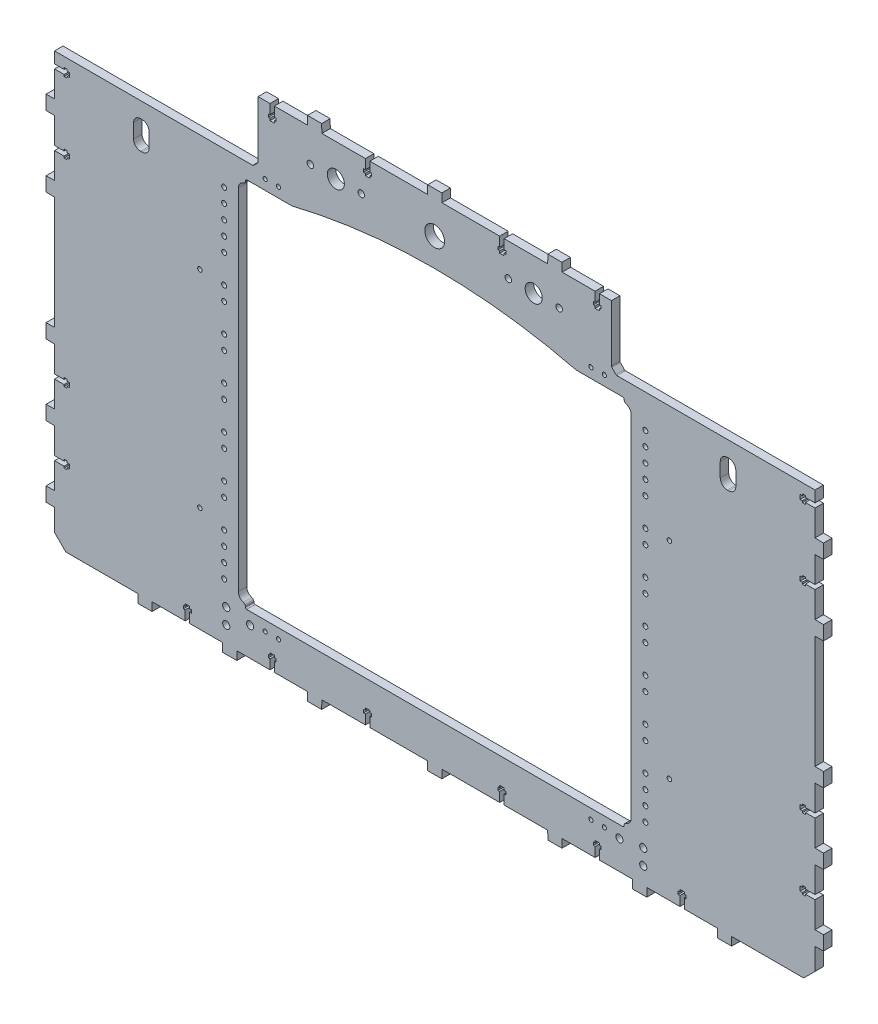
SolidWorks part; units mm, degrees
material "Клен"
ref_plane "Front" through (0, 0, 0) normal (0, 0, 1) x (1, 0, 0)
ref_plane "Top" through (0, 0, 0) normal (0, 1, 0) x (1, 0, 0)
ref_plane "Right" through (0, 0, 0) normal (1, 0, 0) x (0, 0, -1)
sketch "Эскиз1" plane through (0, 0, 0) normal (0, 0, 1) x (1, 0, 0)
  line L0 (1859.5805, 14.5374) -> (1859.5805, 267.5072) construction
  line L1 (1846.6822, 122.5572) -> (1912.7745, 122.5572) construction
  line L2 (1846.6822, 268.5572) -> (1912.7745, 268.5572) construction
  line L3 (1859.5805, 267.5072) -> (1859.5805, 273.1347) construction
  line L6 (1560.5805, 76.7865) -> (1826.5797, 76.7865)
  line L7 (1827.5797, 78.0783) -> (1827.5797, 77.7865)
  line L8 (1832.5805, 332.0072) -> (1832.5797, 84.7865)
  line L9 (1827.5805, 339.0072) -> (1827.5805, 338.7154)
  line L10 (1826.5805, 340.0072) -> (1793.6805, 340.0072)
  line L11 (1560.5805, 340.0072) -> (1592.5638, 340.0072)
  line L13 (1559.5805, 339.0072) -> (1559.5805, 338.7154)
  line L15 (1554.5805, 84.7865) -> (1554.5805, 332.0072)
  line L17 (1559.5805, 78.0783) -> (1559.5805, 77.7865)
  line L18 (1524.5805, 401.0072) -> (1524.5805, 24.1014) construction
  line L19 (1862.5805, 416.6106) -> (1862.5805, 5.7676) construction
  line L20 (1424.5805, 401.0072) -> (1424.5805, 24.1014) construction
  line L21 (1962.5805, 416.6106) -> (1962.5805, 5.7676) construction
  line L22 (1433.5805, 343.0572) -> (1435.0805, 343.0572)
  line L23 (1433.5805, 289.9572) -> (1433.5805, 288.7572)
  line L24 (1433.5805, 149.9572) -> (1433.5805, 148.7572)
  line L25 (1424.5805, 121.4072) -> (1424.5805, 103.0572)
  line L26 (1431.3805, 293.0572) -> (1431.3805, 294.2572)
  line L27 (1431.3805, 154.2572) -> (1433.5805, 154.2572)
  line L28 (1418.5805, 71.5072) -> (1424.5805, 71.4072)
  line L29 (1418.5805, 321.5072) -> (1418.5805, 311.5072)
  line L30 (1418.5805, 311.5072) -> (1424.5805, 311.4072)
  line L31 (1424.5805, 149.9572) -> (1424.5805, 131.6072)
  line L32 (1418.5805, 81.5072) -> (1418.5805, 71.5072)
  line L33 (1433.5805, 338.7572) -> (1431.3805, 338.7572)
  line L34 (1424.5805, 293.0572) -> (1431.3805, 293.0572)
  line L35 (1424.5805, 153.0572) -> (1431.3805, 153.0572)
  line L36 (1433.5805, 103.0572) -> (1435.0805, 103.0572)
  line L37 (1424.5805, 99.9572) -> (1424.5805, 81.6072)
  line L38 (1424.5805, 321.6072) -> (1418.5805, 321.5072)
  line L39 (1433.5805, 293.0572) -> (1435.0805, 293.0572)
  line L40 (1433.5805, 148.7572) -> (1431.3805, 148.7572)
  line L41 (1435.0805, 343.0572) -> (1435.0805, 339.9572)
  line L42 (1431.3805, 289.9572) -> (1424.5805, 289.9572)
  line L43 (1424.5805, 181.6072) -> (1418.5805, 181.5072)
  line L44 (1431.3805, 103.0572) -> (1431.3805, 104.2572)
  line L45 (1435.0805, 103.0572) -> (1435.0805, 99.9572)
  line L46 (1431.3805, 343.0572) -> (1431.3805, 344.2572)
  line L47 (1424.5805, 261.4072) -> (1424.5805, 181.6072)
  line L48 (1433.5805, 153.0572) -> (1435.0805, 153.0572)
  line L49 (1424.5805, 103.0572) -> (1431.3805, 103.0572)
  line L50 (1433.5805, 104.2572) -> (1433.5805, 103.0572)
  line L51 (1424.5805, 311.4072) -> (1424.5805, 293.0572)
  line L52 (1433.5805, 294.2572) -> (1433.5805, 293.0572)
  line L53 (1424.5805, 131.6072) -> (1418.5805, 131.5072)
  line L54 (1431.3805, 338.7572) -> (1431.3805, 339.9572)
  line L55 (1418.5805, 271.5072) -> (1418.5805, 261.5072)
  line L56 (1433.5805, 154.2572) -> (1433.5805, 153.0572)
  line L57 (1433.5805, 98.7572) -> (1431.3805, 98.7572)
  line L58 (1424.5805, 81.6072) -> (1418.5805, 81.5072)
  line L59 (1424.5805, 343.0572) -> (1431.3805, 343.0572)
  line L60 (1431.3805, 339.9572) -> (1424.5805, 339.9572)
  line L61 (1435.0805, 289.9572) -> (1433.5805, 289.9572)
  line L62 (1431.3805, 148.7572) -> (1431.3805, 149.9572)
  line L63 (1435.0805, 339.9572) -> (1433.5805, 339.9572)
  line L64 (1431.3805, 294.2572) -> (1433.5805, 294.2572)
  line L65 (1424.5805, 289.9572) -> (1424.5805, 271.6072)
  line L66 (1433.5805, 99.9572) -> (1433.5805, 98.7572)
  line L67 (1431.3805, 98.7572) -> (1431.3805, 99.9572)
  line L68 (1433.5805, 344.2572) -> (1433.5805, 343.0572)
  line L69 (1424.5805, 271.6072) -> (1418.5805, 271.5072)
  line L70 (1435.0805, 153.0572) -> (1435.0805, 149.9572)
  line L71 (1424.5805, 71.4072) -> (1424.5805, 56.0072)
  line L72 (1431.3805, 344.2572) -> (1433.5805, 344.2572)
  line L73 (1435.0805, 293.0572) -> (1435.0805, 289.9572)
  line L74 (1433.5805, 288.7572) -> (1431.3805, 288.7572)
  line L75 (1418.5805, 131.5072) -> (1418.5805, 121.5072)
  line L76 (1435.0805, 99.9572) -> (1433.5805, 99.9572)
  line L77 (1424.5805, 351.0072) -> (1424.5805, 343.0572)
  line L78 (1418.5805, 171.5072) -> (1424.5805, 171.4072)
  line L79 (1418.5805, 121.5072) -> (1424.5805, 121.4072)
  line L80 (1431.3805, 104.2572) -> (1433.5805, 104.2572)
  line L81 (1431.3805, 288.7572) -> (1431.3805, 289.9572)
  line L82 (1424.5805, 171.4072) -> (1424.5805, 153.0572)
  line L83 (1431.3805, 149.9572) -> (1424.5805, 149.9572)
  line L84 (1433.5805, 339.9572) -> (1433.5805, 338.7572)
  line L85 (1418.5805, 261.5072) -> (1424.5805, 261.4072)
  line L86 (1418.5805, 181.5072) -> (1418.5805, 171.5072)
  line L87 (1431.3805, 99.9572) -> (1424.5805, 99.9572)
  line L88 (1424.5805, 339.9572) -> (1424.5805, 321.6072)
  line L89 (1431.3805, 153.0572) -> (1431.3805, 154.2572)
  line L90 (1435.0805, 149.9572) -> (1433.5805, 149.9572)
  line L91 (1424.5805, 56.0072) -> (1432.5805, 48.0072)
  line L92 (1424.5805, 351.0072) -> (1524.5805, 351.0072)
  line L93 (1432.5805, 48.0072) -> (1483.4805, 48.0072)
  line L94 (1953.5805, 99.9572) -> (1952.0805, 99.9572)
  line L95 (1955.7805, 154.2572) -> (1955.7805, 153.0572)
  line L96 (1953.5805, 289.9572) -> (1952.0805, 289.9572)
  line L97 (1953.5805, 343.0572) -> (1953.5805, 344.2572)
  line L98 (1962.5805, 99.9572) -> (1955.7805, 99.9572)
  line L99 (1955.7805, 153.0572) -> (1962.5805, 153.0572)
  line L100 (1953.5805, 294.2572) -> (1955.7805, 294.2572)
  line L101 (1955.7805, 338.7572) -> (1953.5805, 338.7572)
  line L102 (1953.5805, 103.0572) -> (1953.5805, 104.2572)
  line L103 (1952.0805, 153.0572) -> (1953.5805, 153.0572)
  line L104 (1955.7805, 288.7572) -> (1953.5805, 288.7572)
  line L105 (1962.5805, 321.6072) -> (1962.5805, 339.9572)
  line L106 (1955.7805, 344.2572) -> (1955.7805, 343.0572)
  line L107 (1968.5805, 131.5072) -> (1962.5805, 131.6072)
  line L108 (1962.5805, 149.9572) -> (1955.7805, 149.9572)
  line L109 (1968.5805, 261.5072) -> (1968.5805, 271.5072)
  line L110 (1962.5805, 289.9572) -> (1955.7805, 289.9572)
  line L111 (1955.7805, 343.0572) -> (1962.5805, 343.0572)
  line L112 (1952.0805, 99.9572) -> (1952.0805, 103.0572)
  line L113 (1955.7805, 149.9572) -> (1955.7805, 148.7572)
  line L114 (1952.0805, 293.0572) -> (1953.5805, 293.0572)
  line L115 (1953.5805, 339.9572) -> (1952.0805, 339.9572)
  line L116 (1962.5805, 56.0072) -> (1962.5805, 71.4072)
  line L117 (1955.7805, 103.0572) -> (1962.5805, 103.0572)
  line L118 (1968.5805, 181.5072) -> (1962.5805, 181.6072)
  line L119 (1955.7805, 293.0572) -> (1962.5805, 293.0572)
  line L120 (1953.5805, 344.2572) -> (1955.7805, 344.2572)
  line L121 (1962.5805, 71.4072) -> (1968.5805, 71.5072)
  line L122 (1962.5805, 131.6072) -> (1962.5805, 149.9572)
  line L123 (1968.5805, 171.5072) -> (1968.5805, 181.5072)
  line L124 (1968.5805, 271.5072) -> (1962.5805, 271.6072)
  line L125 (1953.5805, 104.2572) -> (1955.7805, 104.2572)
  line L126 (1953.5805, 153.0572) -> (1953.5805, 154.2572)
  line L127 (1953.5805, 293.0572) -> (1953.5805, 294.2572)
  line L128 (1953.5805, 98.7572) -> (1953.5805, 99.9572)
  line L129 (1962.5805, 121.4072) -> (1968.5805, 121.5072)
  line L130 (1962.5805, 261.4072) -> (1968.5805, 261.5072)
  line L131 (1952.0805, 289.9572) -> (1952.0805, 293.0572)
  line L132 (1952.0805, 343.0572) -> (1953.5805, 343.0572)
  line L133 (1968.5805, 81.5072) -> (1962.5805, 81.6072)
  line L134 (1955.7805, 148.7572) -> (1953.5805, 148.7572)
  line L135 (1962.5805, 293.0572) -> (1962.5805, 311.4072)
  line L136 (1952.0805, 339.9572) -> (1952.0805, 343.0572)
  line L137 (1955.7805, 98.7572) -> (1953.5805, 98.7572)
  line L138 (1962.5805, 103.0572) -> (1962.5805, 121.4072)
  line L139 (1962.5805, 181.6072) -> (1962.5805, 261.4072)
  line L140 (1962.5805, 311.4072) -> (1968.5805, 311.5072)
  line L141 (1952.0805, 103.0572) -> (1953.5805, 103.0572)
  line L142 (1955.7805, 294.2572) -> (1955.7805, 293.0572)
  line L143 (1962.5805, 339.9572) -> (1955.7805, 339.9572)
  line L144 (1955.7805, 104.2572) -> (1955.7805, 103.0572)
  line L145 (1953.5805, 154.2572) -> (1955.7805, 154.2572)
  line L146 (1955.7805, 289.9572) -> (1955.7805, 288.7572)
  line L147 (1968.5805, 121.5072) -> (1968.5805, 131.5072)
  line L148 (1953.5805, 288.7572) -> (1953.5805, 289.9572)
  line L149 (1955.7805, 339.9572) -> (1955.7805, 338.7572)
  line L150 (1954.5805, 48.0072) -> (1962.5805, 56.0072)
  line L151 (1962.5805, 81.6072) -> (1962.5805, 99.9572)
  line L152 (1953.5805, 149.9572) -> (1952.0805, 149.9572)
  line L153 (1962.5805, 171.4072) -> (1968.5805, 171.5072)
  line L154 (1968.5805, 311.5072) -> (1968.5805, 321.5072)
  line L155 (1955.7805, 99.9572) -> (1955.7805, 98.7572)
  line L156 (1952.0805, 149.9572) -> (1952.0805, 153.0572)
  line L157 (1962.5805, 271.6072) -> (1962.5805, 289.9572)
  line L158 (1968.5805, 321.5072) -> (1962.5805, 321.6072)
  line L159 (1962.5805, 343.0572) -> (1962.5805, 351.0072)
  line L160 (1968.5805, 71.5072) -> (1968.5805, 81.5072)
  line L161 (1953.5805, 148.7572) -> (1953.5805, 149.9572)
  line L162 (1962.5805, 153.0572) -> (1962.5805, 171.4072)
  line L163 (1953.5805, 338.7572) -> (1953.5805, 339.9572)
  line L164 (1862.5805, 351.0072) -> (1962.5805, 351.0072)
  line L165 (1954.5805, 48.0072) -> (1903.6805, 48.0072)
  line L166 (1325.5433, 339.9572) -> (1983.9894, 339.9572) construction
  line L169 (1693.5113, 412.8647) -> (1693.5113, 297.5072) construction
  line L170 (1900.5405, 339.9572) -> (1901.5405, 339.9572)
  line L171 (1895.5405, 334.9572) -> (1895.5405, 324.9572)
  line L172 (1900.5405, 319.9572) -> (1901.5405, 319.9572)
  line L173 (1906.5405, 334.9572) -> (1906.5405, 324.9572)
  line L176 (1486.4822, 319.9572) -> (1485.4822, 319.9572)
  line L177 (1480.4822, 334.9572) -> (1480.4822, 324.9572)
  line L178 (1486.4822, 339.9572) -> (1485.4822, 339.9572)
  line L179 (1491.4822, 334.9572) -> (1491.4822, 324.9572)
  line L180 (1893.4805, 48.0072) -> (1893.5805, 42.0072)
  line L181 (1867.0305, 58.5072) -> (1870.1305, 58.5072)
  line L182 (1903.5805, 42.0072) -> (1903.6805, 48.0072)
  line L183 (1867.0305, 54.8072) -> (1865.8305, 54.8072)
  line L184 (1870.1305, 58.5072) -> (1870.1305, 57.0072)
  line L185 (1871.3305, 54.8072) -> (1870.1305, 54.8072)
  line L186 (1865.8305, 57.0072) -> (1867.0305, 57.0072)
  line L187 (1871.3305, 57.0072) -> (1871.3305, 54.8072)
  line L188 (1867.0305, 48.0072) -> (1867.0305, 54.8072)
  line L189 (1870.1305, 57.0072) -> (1871.3305, 57.0072)
  line L190 (1870.1305, 54.8072) -> (1870.1305, 48.0072)
  line L192 (1865.8305, 54.8072) -> (1865.8305, 57.0072)
  line L193 (1893.5805, 42.0072) -> (1903.5805, 42.0072)
  line L194 (1867.0305, 57.0072) -> (1867.0305, 58.5072)
  line L195 (1867.0305, 48.0072) -> (1854.5805, 48.0072)
  line L196 (1893.4805, 48.0072) -> (1870.1305, 48.0072)
  line L197 (1493.5805, 42.0072) -> (1493.6805, 48.0072)
  line L198 (1521.3305, 57.0072) -> (1521.3305, 54.8072)
  line L199 (1517.0305, 48.0072) -> (1517.0305, 54.8072)
  line L200 (1483.5805, 42.0072) -> (1493.5805, 42.0072)
  line L201 (1515.8305, 57.0072) -> (1517.0305, 57.0072)
  line L202 (1521.3305, 54.8072) -> (1520.1305, 54.8072)
  line L203 (1483.4805, 48.0072) -> (1483.5805, 42.0072)
  line L204 (1517.0305, 57.0072) -> (1517.0305, 58.5072)
  line L205 (1517.0305, 58.5072) -> (1520.1305, 58.5072)
  line L206 (1517.0305, 54.8072) -> (1515.8305, 54.8072)
  line L207 (1520.1305, 54.8072) -> (1520.1305, 48.0072)
  line L209 (1520.1305, 58.5072) -> (1520.1305, 57.0072)
  line L210 (1520.1305, 57.0072) -> (1521.3305, 57.0072)
  line L211 (1515.8305, 54.8072) -> (1515.8305, 57.0072)
  line L212 (1520.1305, 48.0072) -> (1532.5805, 48.0072)
  line L213 (1493.6805, 48.0072) -> (1517.0305, 48.0072)
  line L552 (1568.2876, 354.2143) -> (1565.3733, 351.3001)
  line L553 (1564.6662, 351.0072) -> (1524.5805, 351.0072)
  line L624 (1532.5805, 48.0072) -> (1543.4805, 48.0072)
  line L625 (1543.4805, 48.0072) -> (1543.5805, 42.0072)
  line L626 (1543.5805, 42.0072) -> (1553.5805, 42.0072)
  line L627 (1553.5805, 42.0072) -> (1553.6805, 48.0072)
  line L628 (1553.6805, 48.0072) -> (1577.0305, 48.0072)
  line L629 (1577.0305, 48.0072) -> (1577.0305, 54.8072)
  line L630 (1577.0305, 54.8072) -> (1575.8305, 54.8072)
  line L631 (1575.8305, 54.8072) -> (1575.8305, 57.0072)
  line L632 (1575.8305, 57.0072) -> (1577.0305, 57.0072)
  line L633 (1577.0305, 57.0072) -> (1577.0305, 58.5072)
  line L634 (1577.0305, 58.5072) -> (1580.1305, 58.5072)
  line L635 (1580.1305, 58.5072) -> (1580.1305, 57.0072)
  line L636 (1580.1305, 57.0072) -> (1581.3305, 57.0072)
  line L637 (1581.3305, 57.0072) -> (1581.3305, 54.8072)
  line L638 (1581.3305, 54.8072) -> (1580.1305, 54.8072)
  line L639 (1580.1305, 54.8072) -> (1580.1305, 48.0072)
  line L640 (1580.1305, 48.0072) -> (1603.4805, 48.0072)
  line L641 (1603.4805, 48.0072) -> (1603.5805, 42.0072)
  line L642 (1603.5805, 42.0072) -> (1613.5805, 42.0072)
  line L643 (1613.5805, 42.0072) -> (1613.6805, 48.0072)
  line L644 (1613.6805, 48.0072) -> (1644.5305, 48.0072)
  line L645 (1644.5305, 48.0072) -> (1644.5305, 54.8072)
  line L646 (1644.5305, 54.8072) -> (1643.3305, 54.8072)
  line L647 (1643.3305, 54.8072) -> (1643.3305, 57.0072)
  line L648 (1643.3305, 57.0072) -> (1644.5305, 57.0072)
  line L649 (1644.5305, 57.0072) -> (1644.5305, 58.5072)
  line L650 (1644.5305, 58.5072) -> (1647.6305, 58.5072)
  line L651 (1647.6305, 58.5072) -> (1647.6305, 57.0072)
  line L652 (1647.6305, 57.0072) -> (1648.8305, 57.0072)
  line L653 (1648.8305, 57.0072) -> (1648.8305, 54.8072)
  line L654 (1648.8305, 54.8072) -> (1647.6305, 54.8072)
  line L655 (1647.6305, 54.8072) -> (1647.6305, 48.0072)
  line L656 (1647.6305, 48.0072) -> (1688.4805, 48.0072)
  line L657 (1688.4805, 48.0072) -> (1688.5805, 42.0072)
  line L658 (1688.5805, 42.0072) -> (1698.5805, 42.0072)
  line L659 (1698.5805, 42.0072) -> (1698.6805, 48.0072)
  line L660 (1698.6805, 48.0072) -> (1739.5305, 48.0072)
  line L661 (1739.5305, 48.0072) -> (1739.5305, 54.8072)
  line L662 (1739.5305, 54.8072) -> (1738.3305, 54.8072)
  line L663 (1738.3305, 54.8072) -> (1738.3305, 57.0072)
  line L664 (1738.3305, 57.0072) -> (1739.5305, 57.0072)
  line L665 (1739.5305, 57.0072) -> (1739.5305, 58.5072)
  line L666 (1739.5305, 58.5072) -> (1742.6305, 58.5072)
  line L667 (1742.6305, 58.5072) -> (1742.6305, 57.0072)
  line L668 (1742.6305, 57.0072) -> (1743.8305, 57.0072)
  line L669 (1743.8305, 57.0072) -> (1743.8305, 54.8072)
  line L670 (1743.8305, 54.8072) -> (1742.6305, 54.8072)
  line L671 (1742.6305, 54.8072) -> (1742.6305, 48.0072)
  line L672 (1742.6305, 48.0072) -> (1773.4805, 48.0072)
  line L673 (1773.4805, 48.0072) -> (1773.5805, 42.0072)
  line L674 (1773.5805, 42.0072) -> (1783.5805, 42.0072)
  line L675 (1783.5805, 42.0072) -> (1783.6805, 48.0072)
  line L676 (1783.6805, 48.0072) -> (1807.0305, 48.0072)
  line L677 (1807.0305, 48.0072) -> (1807.0305, 54.8072)
  line L678 (1807.0305, 54.8072) -> (1805.8305, 54.8072)
  line L679 (1805.8305, 54.8072) -> (1805.8305, 57.0072)
  line L680 (1805.8305, 57.0072) -> (1807.0305, 57.0072)
  line L681 (1807.0305, 57.0072) -> (1807.0305, 58.5072)
  line L682 (1807.0305, 58.5072) -> (1810.1305, 58.5072)
  line L683 (1810.1305, 58.5072) -> (1810.1305, 57.0072)
  line L684 (1810.1305, 57.0072) -> (1811.3305, 57.0072)
  line L685 (1811.3305, 57.0072) -> (1811.3305, 54.8072)
  line L686 (1811.3305, 54.8072) -> (1810.1305, 54.8072)
  line L687 (1810.1305, 54.8072) -> (1810.1305, 48.0072)
  line L688 (1810.1305, 48.0072) -> (1833.4805, 48.0072)
  line L689 (1833.4805, 48.0072) -> (1833.5805, 42.0072)
  line L690 (1833.5805, 42.0072) -> (1843.5805, 42.0072)
  line L691 (1843.5805, 42.0072) -> (1843.6805, 48.0072)
  line L692 (1843.6805, 48.0072) -> (1854.5805, 48.0072)
  line L763 (1862.5805, 351.0072) -> (1822.4947, 351.0072)
  line L764 (1821.7876, 351.3001) -> (1818.8733, 354.2143)
  line L765 (1818.5805, 354.9215) -> (1818.5805, 395.0072)
  line L766 (1818.5805, 395.0072) -> (1810.1305, 395.0072)
  line L767 (1810.1305, 395.0072) -> (1810.1305, 388.2072)
  line L768 (1810.1305, 388.2072) -> (1811.3305, 388.2072)
  line L769 (1811.3305, 388.2072) -> (1811.3305, 386.0072)
  line L770 (1811.3305, 386.0072) -> (1810.1305, 386.0072)
  line L771 (1810.1305, 386.0072) -> (1810.1305, 384.5072)
  line L772 (1810.1305, 384.5072) -> (1807.0305, 384.5072)
  line L773 (1807.0305, 384.5072) -> (1807.0305, 386.0072)
  line L774 (1807.0305, 386.0072) -> (1805.8305, 386.0072)
  line L775 (1805.8305, 386.0072) -> (1805.8305, 388.2072)
  line L776 (1805.8305, 388.2072) -> (1807.0305, 388.2072)
  line L777 (1807.0305, 388.2072) -> (1807.0305, 395.0072)
  line L778 (1807.0305, 395.0072) -> (1783.6805, 395.0072)
  line L779 (1783.6805, 395.0072) -> (1783.5805, 401.0072)
  line L780 (1783.5805, 401.0072) -> (1773.5805, 401.0072)
  line L781 (1773.5805, 401.0072) -> (1773.4805, 395.0072)
  line L782 (1773.4805, 395.0072) -> (1742.6305, 395.0072)
  line L783 (1742.6305, 395.0072) -> (1742.6305, 388.2072)
  line L784 (1742.6305, 388.2072) -> (1743.8305, 388.2072)
  line L785 (1743.8305, 388.2072) -> (1743.8305, 386.0072)
  line L786 (1743.8305, 386.0072) -> (1742.6305, 386.0072)
  line L787 (1742.6305, 386.0072) -> (1742.6305, 384.5072)
  line L788 (1742.6305, 384.5072) -> (1739.5305, 384.5072)
  line L789 (1739.5305, 384.5072) -> (1739.5305, 386.0072)
  line L790 (1739.5305, 386.0072) -> (1738.3305, 386.0072)
  line L791 (1738.3305, 386.0072) -> (1738.3305, 388.2072)
  line L792 (1738.3305, 388.2072) -> (1739.5305, 388.2072)
  line L793 (1739.5305, 388.2072) -> (1739.5305, 395.0072)
  line L794 (1739.5305, 395.0072) -> (1698.6805, 395.0072)
  line L795 (1698.6805, 395.0072) -> (1698.5805, 401.0072)
  line L796 (1698.5805, 401.0072) -> (1688.5805, 401.0072)
  line L797 (1688.5805, 401.0072) -> (1688.4805, 395.0072)
  line L798 (1688.4805, 395.0072) -> (1647.6305, 395.0072)
  line L799 (1647.6305, 395.0072) -> (1647.6305, 388.2072)
  line L800 (1647.6305, 388.2072) -> (1648.8305, 388.2072)
  line L801 (1648.8305, 388.2072) -> (1648.8305, 386.0072)
  line L802 (1648.8305, 386.0072) -> (1647.6305, 386.0072)
  line L803 (1647.6305, 386.0072) -> (1647.6305, 384.5072)
  line L804 (1647.6305, 384.5072) -> (1644.5305, 384.5072)
  line L805 (1644.5305, 384.5072) -> (1644.5305, 386.0072)
  line L806 (1644.5305, 386.0072) -> (1643.3305, 386.0072)
  line L807 (1643.3305, 386.0072) -> (1643.3305, 388.2072)
  line L808 (1643.3305, 388.2072) -> (1644.5305, 388.2072)
  line L809 (1644.5305, 388.2072) -> (1644.5305, 395.0072)
  line L810 (1644.5305, 395.0072) -> (1613.6805, 395.0072)
  line L811 (1613.6805, 395.0072) -> (1613.5805, 401.0072)
  line L812 (1613.5805, 401.0072) -> (1603.5805, 401.0072)
  line L813 (1603.5805, 401.0072) -> (1603.4805, 395.0072)
  line L814 (1603.4805, 395.0072) -> (1580.1305, 395.0072)
  line L815 (1580.1305, 395.0072) -> (1580.1305, 388.2072)
  line L816 (1580.1305, 388.2072) -> (1581.3305, 388.2072)
  line L817 (1581.3305, 388.2072) -> (1581.3305, 386.0072)
  line L818 (1581.3305, 386.0072) -> (1580.1305, 386.0072)
  line L819 (1580.1305, 386.0072) -> (1580.1305, 384.5072)
  line L820 (1580.1305, 384.5072) -> (1577.0305, 384.5072)
  line L821 (1577.0305, 384.5072) -> (1577.0305, 386.0072)
  line L822 (1577.0305, 386.0072) -> (1575.8305, 386.0072)
  line L823 (1575.8305, 386.0072) -> (1575.8305, 388.2072)
  line L824 (1575.8305, 388.2072) -> (1577.0305, 388.2072)
  line L825 (1577.0305, 388.2072) -> (1577.0305, 395.0072)
  line L826 (1577.0305, 395.0072) -> (1568.5805, 395.0072)
  line L827 (1568.5805, 395.0072) -> (1568.5805, 354.9215)
  circle A0 centre (1859.5805, 268.5572) radius 1.6
  circle A1 centre (1859.5805, 122.5572) radius 1.6
  circle A2 centre (1527.4422, 268.5572) radius 1.6
  circle A3 centre (1527.4422, 122.5572) radius 1.6
  arc A4 (1901.5405, 319.9572) -> (1906.5405, 324.9572) centre (1901.5405, 324.9572) ccw
  arc A5 (1895.5405, 324.9572) -> (1900.5405, 319.9572) centre (1900.5405, 324.9572) ccw
  arc A6 (1901.5405, 339.9572) -> (1906.5405, 334.9572) centre (1901.5405, 334.9572) cw
  arc A7 (1900.5405, 339.9572) -> (1895.5405, 334.9572) centre (1900.5405, 334.9572) ccw
  arc A8 (1568.2876, 354.2143) -> (1568.5805, 354.9215) centre (1567.5805, 354.9215) ccw
  arc A9 (1564.6662, 351.0072) -> (1565.3733, 351.3001) centre (1564.6662, 352.0072) ccw
  arc A10 (1821.7876, 351.3001) -> (1822.4947, 351.0072) centre (1822.4947, 352.0072) ccw
  arc A11 (1818.5805, 354.9215) -> (1818.8733, 354.2143) centre (1819.5805, 354.9215) ccw
  circle A28 centre (1544.5805, 177.5072) radius 1.75
  circle A29 centre (1544.5805, 147.5072) radius 1.75
  circle A30 centre (1544.5805, 137.5072) radius 1.75
  circle A31 centre (1544.5805, 117.5072) radius 1.75
  circle A32 centre (1544.5805, 107.5072) radius 1.75
  circle A33 centre (1544.5805, 97.5072) radius 1.75
  circle A34 centre (1544.5805, 87.5072) radius 1.75
  circle A35 centre (1546.0805, 71.0072) radius 2.55
  circle A36 centre (1546.0805, 60.0072) radius 2.55
  circle A37 centre (1544.5805, 197.5072) radius 1.75
  circle A38 centre (1544.5805, 207.5072) radius 1.75
  circle A39 centre (1544.5805, 227.5072) radius 1.75
  circle A40 centre (1544.5805, 237.5072) radius 1.75
  circle A41 centre (1544.5805, 257.5072) radius 1.75
  circle A42 centre (1544.5805, 267.5072) radius 1.75
  circle A43 centre (1544.5805, 287.5072) radius 1.75
  circle A44 centre (1544.5805, 297.5072) radius 1.75
  circle A45 centre (1544.5805, 307.5072) radius 1.75
  circle A46 centre (1544.5805, 317.5072) radius 1.75
  circle A47 centre (1544.5805, 327.5072) radius 1.75
  circle A87 centre (1573.5805, 347.0072) radius 1.5
  circle A88 centre (1583.0805, 347.0072) radius 1.5
  circle A89 centre (1605.5805, 372.0072) radius 2.3
  circle A90 centre (1623.5805, 372.0072) radius 6.05
  circle A91 centre (1641.5805, 372.0072) radius 2.3
  circle A92 centre (1693.5113, 372.0072) radius 7
  circle A93 centre (1745.5805, 372.0072) radius 2.3
  circle A94 centre (1763.5805, 372.0072) radius 6.05
  circle A95 centre (1781.5805, 372.0072) radius 2.3
  circle A96 centre (1804.0805, 347.0072) radius 1.5
  circle A97 centre (1813.5805, 347.0072) radius 1.5
  circle A98 centre (1842.5805, 327.5072) radius 1.75
  circle A99 centre (1842.5805, 317.5072) radius 1.75
  circle A100 centre (1842.5805, 307.5072) radius 1.75
  circle A101 centre (1842.5805, 297.5072) radius 1.75
  circle A102 centre (1842.5805, 287.5072) radius 1.75
  circle A103 centre (1842.5805, 267.5072) radius 1.75
  circle A104 centre (1842.5805, 257.5072) radius 1.75
  circle A105 centre (1842.5805, 237.5072) radius 1.75
  circle A106 centre (1842.5805, 227.5072) radius 1.75
  circle A107 centre (1842.5805, 207.5072) radius 1.75
  circle A108 centre (1842.5805, 197.5072) radius 1.75
  circle A109 centre (1842.5805, 177.5072) radius 1.75
  circle A110 centre (1842.5805, 167.5072) radius 1.75
  circle A111 centre (1842.5805, 147.5072) radius 1.75
  circle A112 centre (1842.5805, 137.5072) radius 1.75
  circle A113 centre (1842.5805, 117.5072) radius 1.75
  circle A114 centre (1842.5805, 107.5072) radius 1.75
  circle A115 centre (1842.5805, 97.5072) radius 1.75
  circle A116 centre (1842.5805, 87.5072) radius 1.75
  circle A117 centre (1841.0805, 71.0072) radius 2.55
  circle A118 centre (1841.0805, 60.0072) radius 2.55
  circle A119 centre (1824.2277, 68.2968) radius 2.55
  circle A120 centre (1813.5805, 69.7865) radius 1.5
  circle A121 centre (1804.0805, 69.7865) radius 1.5
  circle A122 centre (1583.0805, 69.7865) radius 1.5
  circle A123 centre (1573.5805, 69.7865) radius 1.5
  circle A124 centre (1562.9305, 68.2968) radius 2.55
  circle A125 centre (1544.5805, 167.5072) radius 1.75
  arc A133 (1826.5797, 76.7865) -> (1827.5797, 77.7865) centre (1826.5797, 77.7865) ccw
  arc A134 (1829.0083, 79.995) -> (1827.5797, 78.0783) centre (1829.5797, 78.0783) ccw
  arc A135 (1829.0083, 79.995) -> (1832.5797, 84.7865) centre (1827.5797, 84.7865) ccw
  arc A136 (1832.5805, 332.0072) -> (1829.009, 336.7988) centre (1827.5805, 332.0072) ccw
  arc A137 (1827.5805, 338.7154) -> (1829.009, 336.7988) centre (1829.5805, 338.7154) ccw
  arc A138 (1827.5805, 339.0072) -> (1826.5805, 340.0072) centre (1826.5805, 339.0072) ccw
  arc A139 (1793.6805, 340.0072) -> (1592.5638, 340.0072) centre (1693.1221, -70.0562) ccw
  arc A141 (1560.5805, 340.0072) -> (1559.5805, 339.0072) centre (1560.5805, 339.0072) ccw
  arc A143 (1558.1519, 336.7988) -> (1559.5805, 338.7154) centre (1557.5805, 338.7154) ccw
  arc A145 (1558.1519, 336.7988) -> (1554.5805, 332.0072) centre (1559.5805, 332.0072) ccw
  arc A147 (1559.5805, 77.7865) -> (1560.5805, 76.7865) centre (1560.5805, 77.7865) ccw
  arc A149 (1554.5805, 84.7865) -> (1558.1519, 79.995) centre (1559.5805, 84.7865) ccw
  arc A151 (1559.5805, 78.0783) -> (1558.1519, 79.995) centre (1557.5805, 78.0783) ccw
  arc A152 (1485.4822, 319.9572) -> (1480.4822, 324.9572) centre (1485.4822, 324.9572) cw
  arc A153 (1485.4822, 339.9572) -> (1480.4822, 334.9572) centre (1485.4822, 334.9572) ccw
  arc A154 (1491.4822, 324.9572) -> (1486.4822, 319.9572) centre (1486.4822, 324.9572) cw
  arc A155 (1486.4822, 339.9572) -> (1491.4822, 334.9572) centre (1486.4822, 334.9572) cw
  point P18 (1892.325, 329.9572)
  dimension "D7" = 5
  dimension "D11" = 3.2
  dimension "D12" = 3.2
  dimension "D2" = 100
  dimension "D3" = 100
  dimension "D4" = 538
  dimension "D5" = 269.0691
  dimension "D6" = 268.9309
  dimension "D8" = 3
  dimension "D9" = 74.55
  dimension "D10" = 146
extrude "Бобышка-Вытянуть1" add sketch "Эскиз1" along normal blind 6
